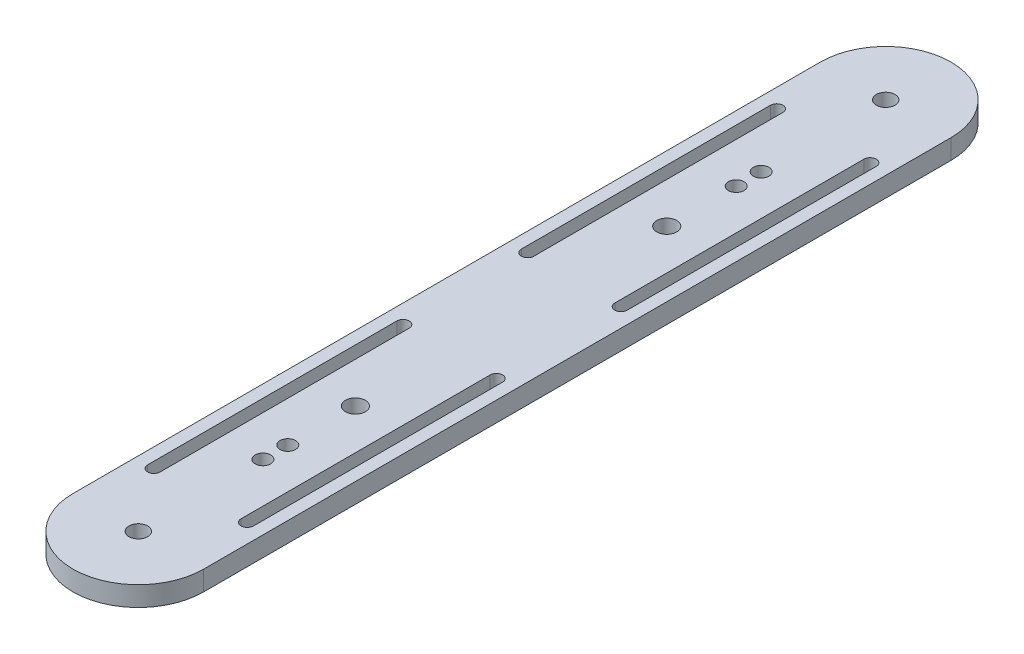
SolidWorks part; units mm, degrees
ref_plane "Front Plane" through (0, 0, 0) normal (0, 0, 1) x (1, 0, 0)
ref_plane "Top Plane" through (0, 0, 0) normal (0, 1, 0) x (1, 0, 0)
ref_plane "Right Plane" through (0, 0, 0) normal (1, 0, 0) x (0, 0, -1)
sketch "Sketch1" plane through (0, 0, 0) normal (0, 1, 0) x (1, 0, 0)
  line L0 (-10.5, 0) -> (-10.5, -120)
  line L1 (10.5, 0) -> (10.5, -120)
  arc A0 (10.5, 0) -> (-10.5, 0) centre (0, 0) ccw
  arc A1 (-10.5, -120) -> (10.5, -120) centre (0, -120) ccw
  circle A2 centre (0, 0) radius 1.5
  circle A5 centre (0, -120) radius 1.5
  dimension "D1" = 10.5
  dimension "D3" = 3
  dimension "D2" = 120
extrude "Boss-Extrude1" add sketch "Sketch1" along normal blind 3.175
sketch "Sketch2" plane through (0, 0, 0) normal (0, -1, 0) x (1, 0, 0)
  arc A0 (0, 18.75) -> (0, 21.25) centre (0, 20) ccw construction
  arc A1 (0, 21.25) -> (0, 18.75) centre (0, 20) ccw construction
  arc A2 (0, 25.25) -> (0, 22.75) centre (0, 24) ccw construction
  arc A3 (0, 22.75) -> (0, 25.25) centre (0, 24) ccw construction
  arc A4 (0, 18.75) -> (0, 21.25) centre (0, 20) ccw
  arc A5 (0, 21.25) -> (0, 18.75) centre (0, 20) ccw
  arc A6 (0, 25.25) -> (0, 22.75) centre (0, 24) ccw
  arc A7 (0, 22.75) -> (0, 25.25) centre (0, 24) ccw
extrude "Cut-Extrude1" cut sketch "Sketch2" against normal through all both and the other way through all
sketch "Sketch3" plane through (0, 3.175, 0) normal (0, 1, 0) x (1, 0, 0)
  arc A0 (0, -97.25) -> (0, -94.75) centre (0, -96) ccw construction
  arc A1 (0, -94.75) -> (0, -97.25) centre (0, -96) ccw construction
  arc A2 (0, -98.75) -> (0, -101.25) centre (0, -100) ccw construction
  arc A3 (0, -101.25) -> (0, -98.75) centre (0, -100) ccw construction
  arc A4 (0, -97.25) -> (0, -94.75) centre (0, -96) ccw
  arc A5 (0, -94.75) -> (0, -97.25) centre (0, -96) ccw
  arc A6 (0, -98.75) -> (0, -101.25) centre (0, -100) ccw
  arc A7 (0, -101.25) -> (0, -98.75) centre (0, -100) ccw
extrude "Cut-Extrude2" cut sketch "Sketch3" against normal through all both and the other way through all
sketch "Sketch4" plane through (0, 3.175, 0) normal (0, 1, 0) x (1, 0, 0)
  circle A0 centre (0, -35.15) radius 1.6 construction
  circle A1 centre (0, -85.15) radius 1.6 construction
  circle A2 centre (0, -35.15) radius 1.6
  circle A3 centre (0, -85.15) radius 1.6
extrude "Cut-Extrude3" cut sketch "Sketch4" against normal through all both and the other way through all
sketch "Sketch5" plane through (0, 0, 0) normal (0, -1, 0) x (1, 0, 0)
  line L0 (0, -10.5) -> (0, 130.5) construction
  line L1 (-10.5, 60) -> (10.5, 60) construction
  line L2 (-10.5, 0) -> (-10.5, 120) construction
  line L3 (10.5, 120) -> (10.5, 0) construction
  line L6 (-8.5, 10) -> (-8.5, 50)
  line L7 (-6.5, 50) -> (-6.5, 10)
  line L8 (6.5, 50) -> (6.5, 10)
  line L9 (8.5, 10) -> (8.5, 50)
  line L22 (8.5, 110) -> (8.5, 70)
  line L23 (6.5, 70) -> (6.5, 110)
  line L24 (-6.5, 70) -> (-6.5, 110)
  line L25 (-8.5, 110) -> (-8.5, 70)
  arc A0 (-10.5, 0) -> (10.5, 0) centre (0, 0) ccw construction
  arc A1 (10.5, 120) -> (-10.5, 120) centre (0, 120) ccw construction
  arc A4 (-8.5, 10) -> (-6.5, 10) centre (-7.5, 10) ccw
  arc A5 (-6.5, 50) -> (-8.5, 50) centre (-7.5, 50) ccw
  arc A6 (6.5, 50) -> (8.5, 50) centre (7.5, 50) cw
  arc A7 (8.5, 10) -> (6.5, 10) centre (7.5, 10) cw
  arc A20 (8.5, 110) -> (6.5, 110) centre (7.5, 110) ccw
  arc A21 (6.5, 70) -> (8.5, 70) centre (7.5, 70) ccw
  arc A22 (-6.5, 70) -> (-8.5, 70) centre (-7.5, 70) cw
  arc A23 (-8.5, 110) -> (-6.5, 110) centre (-7.5, 110) cw
  dimension "D1" = 40
  dimension "D3" = 10
  dimension "D2" = 2
  dimension "D4" = 3
extrude "Cut-Extrude4" cut sketch "Sketch5" against normal blind 40
